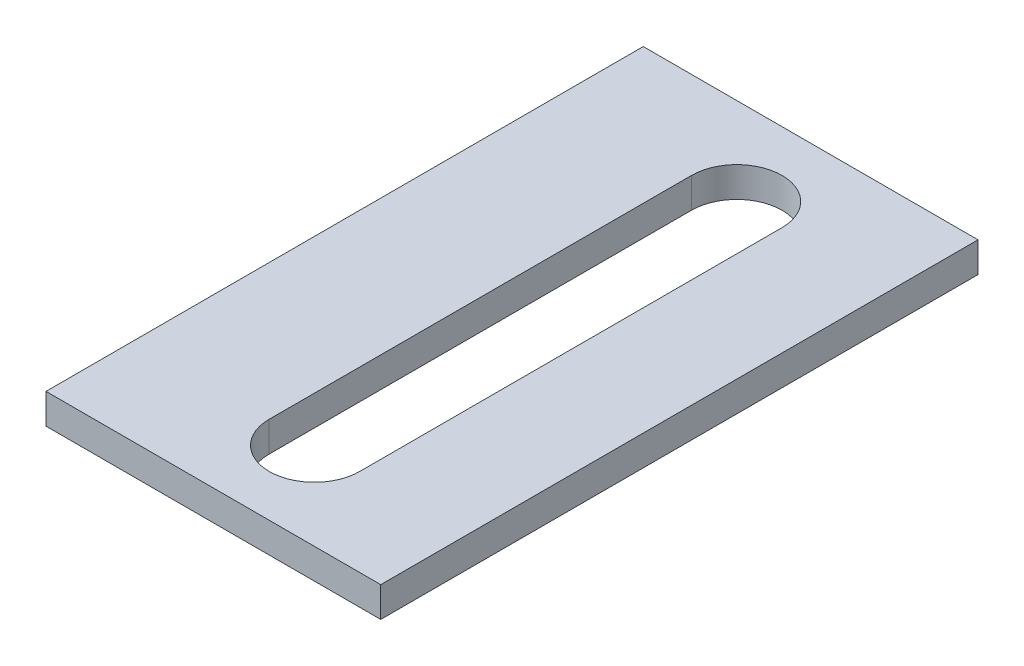
SolidWorks part; units mm, degrees
ref_plane "Front Plane" through (0, 0, 0) normal (0, 0, 1) x (1, 0, 0)
ref_plane "Top Plane" through (0, 0, 0) normal (0, 1, 0) x (1, 0, 0)
ref_plane "Right Plane" through (0, 0, 0) normal (1, 0, 0) x (0, 0, -1)
sketch "Sketch1" plane through (0, 0, 0) normal (1, 0, 0) x (0, 0, -1)
  line L1 (-6.9, -4.4) -> (6.9, -4.4)
  line L2 (-6.9, -4.4) -> (-6.9, 4.4)
  line L3 (-6.9, 4.4) -> (6.9, 4.4)
  line L4 (6.9, -4.4) -> (6.9, 4.4)
  line L5 (-6.9, -4.4) -> (6.9, 4.4) construction
  line L6 (-6.9, 4.4) -> (6.9, -4.4) construction
  point P0 (0, 0)
  dimension "D1" = 13.8
  dimension "D2" = 8.8
extrude "Boss-Extrude1" add sketch "Sketch1" along normal blind 3
sketch "Sketch2" plane through (3, 0, 0) normal (1, 0, 0) x (0, 0, -1)
  line L0 (6.9, 4.4) -> (-6.9, 4.4) construction
  line L1 (1, 4.4) -> (-1, 4.4)
  line L2 (1, 4.4) -> (1, -30.6)
  line L3 (1, -30.6) -> (-1, -30.6)
  line L4 (-1, 4.4) -> (-1, -30.6)
  line L5 (-6.9, -4.4) -> (6.9, -4.4) construction
  line L6 (-6.9, -4.4) -> (6.9, -4.4) construction
  point P8 (0, -4.4)
  point P9 (0, -30.6)
  dimension "D1" = 2
  dimension "D2" = 26.2
extrude "Boss-Extrude2" add sketch "Sketch2" along normal blind 3
sketch "Sketch3" plane through (6, 0, 0) normal (1, 0, 0) x (0, 0, -1)
  line L1 (-0.6, -30.6) -> (0.6, -30.6)
  line L2 (-0.6, -30.6) -> (-0.6, -24.6)
  line L3 (-0.6, -24.6) -> (0.6, -24.6)
  line L4 (0.6, -30.6) -> (0.6, -24.6)
  line L5 (-1, -30.6) -> (1, -30.6) construction
  point P10 (0, -30.6)
  point P11 (0, -30.6)
  dimension "D1" = 1.2
  dimension "D2" = 6
extrude "Boss-Extrude3" add sketch "Sketch3" along normal blind 7
fillet "Fillet3" radius 10 1 edges at (3, -4.4, 0)
sketch "Sketch5" plane through (0, 4.4, 0) normal (0, 1, 0) x (1, 0, 0)
  line L0 (3, 6.9) -> (0, 6.9) construction
  line L1 (3, -6.9) -> (-12, -6.9)
  line L2 (3, -6.9) -> (3, 6.9)
  line L3 (3, 6.9) -> (-12, 6.9)
  line L4 (-12, -6.9) -> (-12, 6.9)
  dimension "D1" = 15
extrude "Boss-Extrude4" add sketch "Sketch5" along normal blind 4
sketch "Sketch6" plane through (0, 4.4, 0) normal (0, -1, 0) x (1, 0, 0)
  line L0 (-6, 3) -> (-6, -3) construction
  line L1 (0, -6.9) -> (0, 6.9) construction
  circle A0 centre (-6, 3) radius 1.5
  circle A1 centre (-6, -3) radius 1.5
  point P4 (0, 0)
  point P7 (-6, 0)
  dimension "D1" = 3
  dimension "D2" = 6
  dimension "D3" = 6
extrude "Cut-Extrude4" cut sketch "Sketch6" against normal through all
sketch "Sketch8" plane through (0, 0, -1) normal (0, 0, -1) x (-1, 0, 0)
  line L0 (-3, -18.7582) -> (0, -4.4)
  line L1 (-3, -30.6) -> (-3, -11.5414) construction
  line L2 (0, -4.4) -> (-3, -4.4)
  line L3 (-3, -4.4) -> (-3, -18.7582)
extrude "Boss-Extrude5" add sketch "Sketch8" against normal up to surface (2 mm away) up to face at (3.5314, -10.3485, 1)
chamfer "Chamfer2" distance 3 angle 45 1 edges at (3, 4.4, 0)
sketch "Sketch11" plane through (0, 0, -0.6) normal (0, 0, -1) x (-1, 0, 0)
  line L0 (-6, -24.6) -> (-13, -24.6)
  line L1 (-13, -24.6) -> (-6, 1.7425)
  line L2 (-6, 1.7425) -> (-6, -24.6)
extrude "Boss-Extrude7" add sketch "Sketch11" against normal up to surface (1.2 mm away) up to face at (9.5, -27.6, 0.6)
sketch "Sketch12" plane through (0, 0, -6.9) normal (0, 0, -1) x (-1, 0, 0)
  line L0 (-3, -4.4) -> (-3, 8.4) construction
  line L1 (12, 8.4) -> (-3, 8.4)
  line L2 (12, 8.4) -> (12, 4.4)
  line L3 (12, 4.4) -> (-3, 4.4)
  line L4 (-3, 8.4) -> (-3, 4.4)
  line L5 (0, 4.4) -> (12, 4.4) construction
extrude "Boss-Extrude8" add sketch "Sketch12" along normal blind 3
sketch "Sketch13" plane through (0, 0, 6.9) normal (0, 0, 1) x (1, 0, 0)
  line L0 (3, 8.4) -> (3, -4.4) construction
  line L1 (-12, 8.4) -> (3, 8.4)
  line L2 (-12, 8.4) -> (-12, 4.4)
  line L3 (-12, 4.4) -> (3, 4.4)
  line L4 (3, 8.4) -> (3, 4.4)
  line L5 (-12, 4.4) -> (0, 4.4) construction
extrude "Boss-Extrude9" add sketch "Sketch13" along normal blind 3
sketch "Sketch14" plane through (0, 8.4, 0) normal (0, 1, 0) x (1, 0, 0)
  line L0 (-6, 3) -> (-6, -3) construction
  line L2 (-7.5, 7) -> (-7.5, -7)
  line L4 (-4.5, 7) -> (-4.5, -7)
  arc A0 (-7.5, 7) -> (-4.5, 7) centre (-6, 7) cw
  arc A1 (-4.5, -7) -> (-7.5, -7) centre (-6, -7) cw
  point P8 (-6, 0)
  point P10 (-4.5, 0)
  dimension "D1" = 3
  dimension "D2" = 14
extrude "Cut-Extrude7" cut sketch "Sketch14" against normal through all both and the other way through all
sketch "Sketch15" plane through (0, -30.6, 0) normal (0, -1, 0) x (1, 0, 0)
  line L0 (13, 0.6) -> (13, -0.6) construction
  line L1 (13, 0.32) -> (12.1921, 0.32)
  line L2 (13, 0.32) -> (13, -0.32)
  line L3 (13, -0.32) -> (12.1921, -0.32)
  line L4 (12.1921, 0.32) -> (12.1921, -0.32)
  line L5 (11.9922, 0.6) -> (11.9922, -0.6) construction
  line L6 (13, 0.6) -> (6, 0.6) construction
  line L7 (13, -0.6) -> (6, -0.6) construction
  point P13 (13, 0)
  point P14 (11.9922, 0)
  dimension "D1" = 0.28
extrude "Cut-Extrude8" cut sketch "Sketch15" against normal through all both and the other way through all
sketch "Sketch16" plane through (12.1921, 0, 0) normal (1, 0, 0) x (0, 0, -1)
  line L0 (0.32, -21.5597) -> (0.32, -30.6) construction
  line L1 (-0.32, -30.6) -> (0.32, -30.6)
  line L2 (-0.32, -30.6) -> (-0.32, -30)
  line L3 (-0.32, -30) -> (0.32, -30)
  line L4 (0.32, -30.6) -> (0.32, -30)
  dimension "D1" = 0.6
extrude "Cut-Extrude9" cut sketch "Sketch16" against normal through all both and the other way through all
chamfer "Chamfer3" distance 1 angle 45 1 edges at (12.1921, -30, 0)
sketch "Sketch17" plane through (0, 4.4, 0) normal (0, -1, 0) x (1, 0, 0)
  line L1 (20.8467, 21.9752) -> (-20.8467, 21.9752)
  line L2 (20.8467, 21.9752) -> (20.8467, -21.9752)
  line L3 (20.8467, -21.9752) -> (-20.8467, -21.9752)
  line L4 (-20.8467, 21.9752) -> (-20.8467, -21.9752)
  line L5 (20.8467, 21.9752) -> (-20.8467, -21.9752) construction
  line L6 (20.8467, -21.9752) -> (-20.8467, 21.9752) construction
sketch "Sketch18" plane through (0, 0, 9.9) normal (0, 0, 1) x (1, 0, 0)
  line L0 (3, 8.4) -> (-12, 8.4) construction
  line L1 (-0.9029, 8.4) -> (19.7991, 8.4)
  line L2 (-0.9029, 8.4) -> (-0.9029, -33.328)
  line L3 (-0.9029, -33.328) -> (19.7991, -33.328)
  line L4 (19.7991, 8.4) -> (19.7991, -33.328)
extrude "Cut-Extrude10" cut sketch "Sketch18" against normal blind 36
sketch "Sketch19" plane through (0, 4.4, 0) normal (0, -1, 0) x (1, 0, 0)
  line L0 (-0.9029, -9.9) -> (-0.9029, 9.9) construction
  line L1 (-12, -9.9) -> (-0.9029, -9.9)
  line L2 (-12, -9.9) -> (-12, 11.0285)
  line L3 (-12, 11.0285) -> (-0.9029, 11.0285)
  line L4 (-0.9029, -9.9) -> (-0.9029, 11.0285)
extrude "Cut-Extrude11" cut sketch "Sketch19" against normal blind 3
